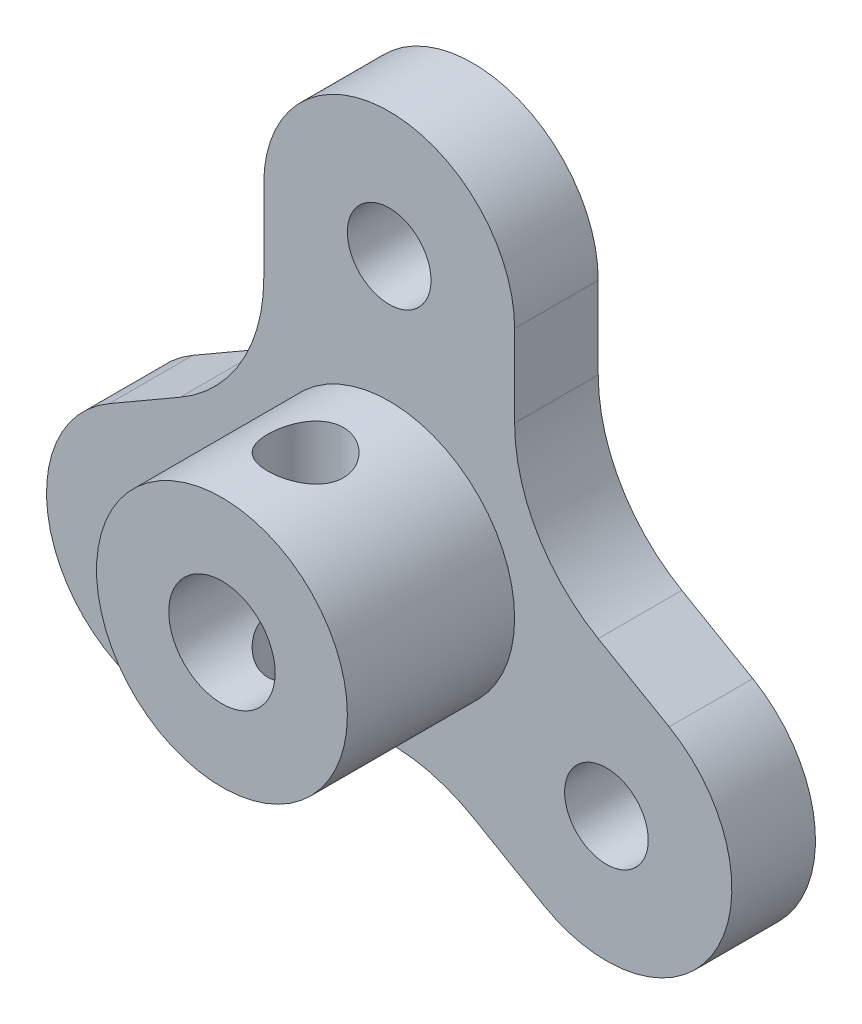
SolidWorks part; units mm, degrees
material "6061-T6 (SS)"
ref_plane "Front Plane" through (0, 0, 0) normal (0, 0, 1) x (1, 0, 0)
ref_plane "Top Plane" through (0, 0, 0) normal (0, 1, 0) x (1, 0, 0)
ref_plane "Right Plane" through (0, 0, 0) normal (1, 0, 0) x (0, 0, -1)
sketch "Sketch1" plane through (0, 0, 0) normal (1, 0, 0) x (0, 0, -1)
  line L0 (0, 2.0193) -> (0, 4.7625)
  line L1 (0, 4.7625) -> (6.35, 4.7625)
  line L3 (6.35, 4.7625) -> (6.35, 15.875)
  line L4 (9.525, 15.875) -> (9.525, 2.0193)
  line L5 (0, 2.0193) -> (9.525, 2.0193)
  line L6 (6.35, 15.875) -> (9.525, 15.875)
  line L7 (0, 0) -> (10.5039, 0) construction
  dimension "D1" = 2.0193
  dimension "D2" = 4.7625
  dimension "D3" = 6.35
  dimension "D4" = 3.175
  dimension "D5" = 15.875
revolve "Revolve1" add sketch "Sketch1" angle 360 about L7
hole_wizard "1/8 (0.1250) Dowel Hole1" positions "Sketch2" profile "Sketch3" hole size "1/8" standard "ANSI Inch" end condition through all
sketch "Sketch2" plane through (0, 0, -6.35) normal (0, 0, 1) x (1, 0, 0)
  point P0 (0, 9.525)
  point P9 (0, 0)
  dimension "D2" = 9.525
sketch "Sketch3" plane through (0, 9.525, -6.35) normal (1, 0, 0) x (0, -1, 0)
  line L0 (0, 0) -> (0, 3.175)
  line L1 (0, 3.175) -> (1.5875, 3.175)
  line L2 (1.5875, 3.175) -> (1.5875, 0)
  line L5 (1.5875, 0) -> (0, 0)
  line L11 (0, -6.35) -> (0, 107.95) construction
  dimension "Thru Hole Dia." = 3.175
  dimension "Thru Hole Depth" = 3.175
hole_wizard "#6-40 Tapped Hole1" positions "Sketch4" profile "Sketch6" tap size "#6-40" standard "ANSI Inch" end condition through all
sketch "Sketch4" plane through (0, 0, 0) normal (0, 1, 0) x (1, 0, 0)
  point P0 (0, 3.175)
  dimension "D1" = 3.175
sketch "Sketch6" plane through (0, 0, -3.175) normal (1, 0, 0) x (0, 0, -1)
  line L0 (0, 0) -> (0, 15.875)
  line L1 (0, 15.875) -> (1.4351, 15.875)
  line L2 (1.4351, 15.875) -> (1.4351, 0)
  line L5 (1.4351, 0) -> (0, 0)
  line L11 (0, -6.35) -> (0, 107.95) construction
  dimension "Thru Tap Drill Dia." = 2.8702
  dimension "Thru Tap Drill Depth" = 15.875
cosmetic thread "Hole Thread2" parameters "D2"=3.5052
pattern_circular "CirPattern1" count 2 over 360 about axis through (0, 0, 0) along (0, 0, 1) of "#6-40 Tapped Hole1"
pattern_circular "CirPattern2" count 3 over 360 about axis through (0, 0, 0) along (0, 0, 1) of "1/8 (0.1250) Dowel Hole1"
sketch "Sketch7" plane through (0, 0, -6.35) normal (0, 0, 1) x (1, 0, 0)
  line L0 (4.7625, 9.525) -> (4.7625, 2.7496)
  line L1 (-4.7625, 9.525) -> (-4.7625, 2.7496)
  line L2 (10.6301, -0.6381) -> (4.7625, 2.7496)
  line L3 (-10.6301, -0.6381) -> (-4.7625, 2.7496)
  line L4 (5.8676, -8.8869) -> (0, -5.4993)
  line L5 (-5.8676, -8.8869) -> (0, -5.4993)
  circle A0 centre (-8.2489, -4.7625) radius 1.5875 construction
  circle A1 centre (8.2489, -4.7625) radius 1.5875 construction
  circle A2 centre (0, 9.525) radius 1.5875 construction
  circle A3 centre (-8.2489, -4.7625) radius 1.5875
  circle A4 centre (8.2489, -4.7625) radius 1.5875
  circle A5 centre (0, 9.525) radius 1.5875
  arc A6 (-4.7625, 9.525) -> (4.7625, 9.525) centre (0, 9.525) cw
  arc A7 (5.8676, -8.8869) -> (10.6301, -0.6381) centre (8.2489, -4.7625) ccw
  arc A8 (-5.8676, -8.8869) -> (-10.6301, -0.6381) centre (-8.2489, -4.7625) cw
  circle M5 centre (0, 0) radius 15.875
  dimension "D1" = 4.7625
  dimension "D2" = 4.7625
  dimension "D3" = 4.7625
  dimension "D4" = 120
  dimension "D5" = 120
extrude "Cut-Extrude1" cut sketch "Sketch7" against normal blind 10 contours A8 L3 L1 A6 M5 | A7 A6 L0 L2 M5 | L5 A8 A7 L4 M5 region at (-15.426, 0, -6.35)
fillet "Fillet1" radius 6.35 3 edges at (-4.7625, 2.7496, -7.9375) (0, -5.4993, -7.9375) (4.7625, 2.7496, -7.9375)
equation "\"D2@Sketch7\"=\"D1@Sketch7\""
equation "\"D3@Sketch7\"=\"D1@Sketch7\""
